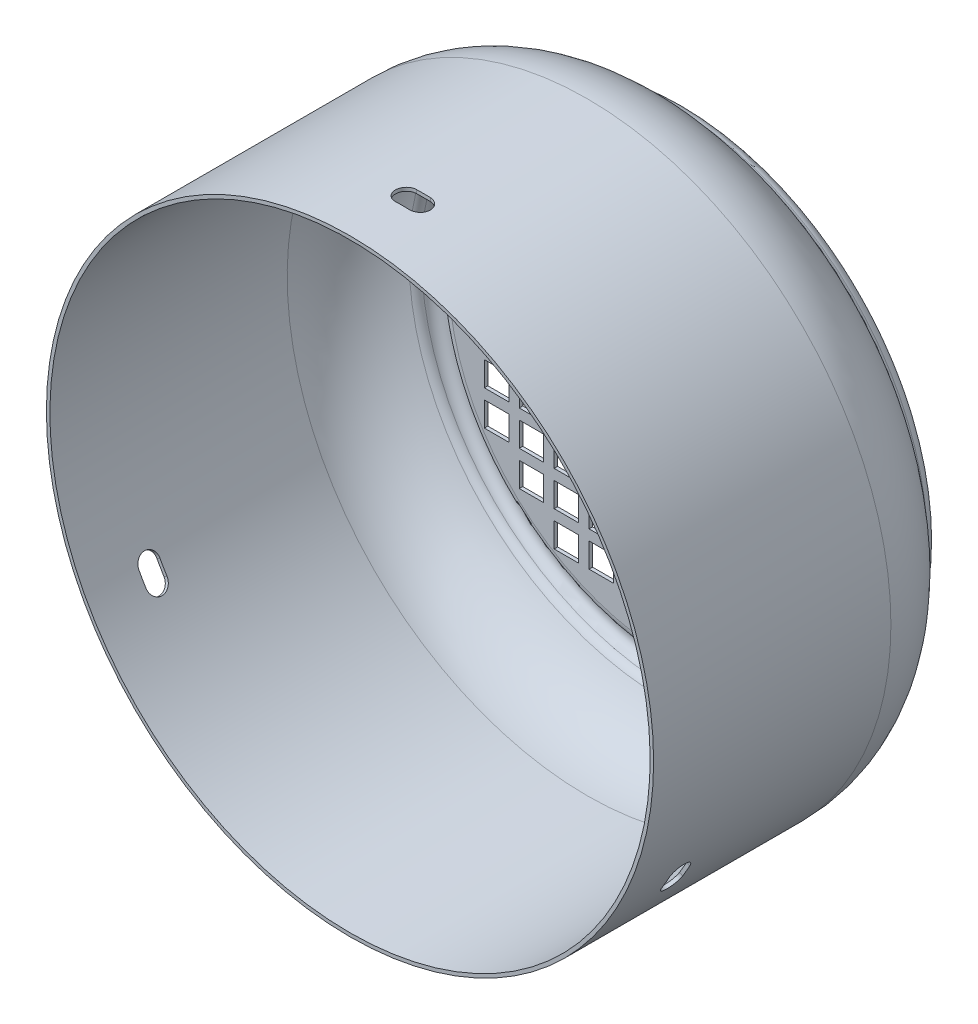
SolidWorks part; units mm, degrees
material "Q235"
ref_plane "前视基准面" through (0, 0, 0) normal (0, 0, 1) x (1, 0, 0)
ref_plane "上视基准面" through (0, 0, 0) normal (0, 1, 0) x (1, 0, 0)
ref_plane "右视基准面" through (0, 0, 0) normal (1, 0, 0) x (0, 0, -1)
sketch "草图1" plane through (0, 0, 0) normal (1, 0, 0) x (0, 0, -1)
  line L0 (0, 86) -> (0, 0)
  line L1 (0, 0) -> (92, 0) construction
  line L4 (92, 63.8038) -> (92, 0)
  line L5 (0, 86) -> (68, 86)
  arc A0 (93.5, 66.4019) -> (92.4282, 71.9693) centre (92, 69) ccw
  arc A1 (90.285, 73.3932) -> (68, 86) centre (68, 60) ccw
  arc A2 (90.285, 73.3932) -> (92.4282, 71.9693) centre (92.8564, 74.9386) ccw
  arc A3 (92, 63.8038) -> (93.5, 66.4019) centre (95, 63.8038) cw
  point P15 (92, 66)
  dimension "D1" = 3
revolve "旋转-薄壁2" add sketch "草图1" angle 360 about L1 wall 1
sketch "草图2" plane through (0, 0, -93) normal (0, 0, -1) x (-1, 0, 0)
  line L0 (-3.5, 3.5) -> (3.5, 3.5)
  line L1 (3.5, 3.5) -> (3.5, -3.5)
  line L2 (3.5, -3.5) -> (-3.5, -3.5)
  line L3 (-3.5, -3.5) -> (-3.5, 3.5)
  line L4 (13.5, -3.5) -> (6.5, -3.5)
  line L5 (13.5, 3.5) -> (13.5, -3.5)
  line L6 (6.5, -3.5) -> (6.5, 3.5)
  line L7 (6.5, 3.5) -> (13.5, 3.5)
  line L8 (23.5, -3.5) -> (16.5, -3.5)
  line L9 (23.5, 3.5) -> (23.5, -3.5)
  line L10 (16.5, -3.5) -> (16.5, 3.5)
  line L11 (16.5, 3.5) -> (23.5, 3.5)
  line L12 (33.5, -3.5) -> (26.5, -3.5)
  line L13 (33.5, 3.5) -> (33.5, -3.5)
  line L14 (26.5, -3.5) -> (26.5, 3.5)
  line L15 (26.5, 3.5) -> (33.5, 3.5)
  line L16 (43.5, -3.5) -> (36.5, -3.5)
  line L17 (43.5, 3.5) -> (43.5, -3.5)
  line L18 (36.5, -3.5) -> (36.5, 3.5)
  line L19 (36.5, 3.5) -> (43.5, 3.5)
  line L20 (53.5, -3.5) -> (46.5, -3.5)
  line L21 (53.5, 3.5) -> (53.5, -3.5)
  line L22 (46.5, -3.5) -> (46.5, 3.5)
  line L23 (46.5, 3.5) -> (53.5, 3.5)
  line L24 (3.5, 6.5) -> (-3.5, 6.5)
  line L25 (3.5, 13.5) -> (3.5, 6.5)
  line L26 (-3.5, 6.5) -> (-3.5, 13.5)
  line L27 (-3.5, 13.5) -> (3.5, 13.5)
  line L32 (23.5, 6.5) -> (16.5, 6.5)
  line L33 (23.5, 13.5) -> (23.5, 6.5)
  line L34 (16.5, 6.5) -> (16.5, 13.5)
  line L35 (16.5, 13.5) -> (23.5, 13.5)
  line L36 (33.5, 6.5) -> (26.5, 6.5)
  line L37 (33.5, 13.5) -> (33.5, 6.5)
  line L38 (26.5, 6.5) -> (26.5, 13.5)
  line L39 (26.5, 13.5) -> (33.5, 13.5)
  line L40 (43.5, 6.5) -> (36.5, 6.5)
  line L41 (43.5, 13.5) -> (43.5, 6.5)
  line L42 (36.5, 6.5) -> (36.5, 13.5)
  line L43 (36.5, 13.5) -> (43.5, 13.5)
  line L44 (53.5, 6.5) -> (46.5, 6.5)
  line L45 (53.5, 13.5) -> (53.5, 6.5)
  line L46 (46.5, 6.5) -> (46.5, 13.5)
  line L47 (46.5, 13.5) -> (53.5, 13.5)
  line L48 (3.5, 16.5) -> (-3.5, 16.5)
  line L49 (3.5, 23.5) -> (3.5, 16.5)
  line L50 (-3.5, 16.5) -> (-3.5, 23.5)
  line L51 (-3.5, 23.5) -> (3.5, 23.5)
  line L52 (13.5, 16.5) -> (6.5, 16.5)
  line L53 (13.5, 23.5) -> (13.5, 16.5)
  line L54 (6.5, 16.5) -> (6.5, 23.5)
  line L55 (6.5, 23.5) -> (13.5, 23.5)
  line L56 (23.5, 16.5) -> (16.5, 16.5)
  line L57 (23.5, 23.5) -> (23.5, 16.5)
  line L58 (16.5, 16.5) -> (16.5, 23.5)
  line L59 (16.5, 23.5) -> (23.5, 23.5)
  line L60 (33.5, 16.5) -> (26.5, 16.5)
  line L61 (33.5, 23.5) -> (33.5, 16.5)
  line L62 (26.5, 16.5) -> (26.5, 23.5)
  line L63 (26.5, 23.5) -> (33.5, 23.5)
  line L64 (43.5, 16.5) -> (36.5, 16.5)
  line L65 (43.5, 23.5) -> (43.5, 16.5)
  line L66 (36.5, 16.5) -> (36.5, 23.5)
  line L67 (36.5, 23.5) -> (43.5, 23.5)
  line L68 (53.5, 16.5) -> (46.5, 16.5)
  line L69 (53.5, 23.5) -> (53.5, 16.5)
  line L70 (46.5, 16.5) -> (46.5, 23.5)
  line L71 (46.5, 23.5) -> (53.5, 23.5)
  line L72 (3.5, 26.5) -> (-3.5, 26.5)
  line L73 (3.5, 33.5) -> (3.5, 26.5)
  line L74 (-3.5, 26.5) -> (-3.5, 33.5)
  line L75 (-3.5, 33.5) -> (3.5, 33.5)
  line L76 (13.5, 26.5) -> (6.5, 26.5)
  line L77 (13.5, 33.5) -> (13.5, 26.5)
  line L78 (6.5, 26.5) -> (6.5, 33.5)
  line L79 (6.5, 33.5) -> (13.5, 33.5)
  line L80 (23.5, 26.5) -> (16.5, 26.5)
  line L81 (23.5, 33.5) -> (23.5, 26.5)
  line L82 (16.5, 26.5) -> (16.5, 33.5)
  line L83 (16.5, 33.5) -> (23.5, 33.5)
  line L84 (33.5, 26.5) -> (26.5, 26.5)
  line L85 (33.5, 33.5) -> (33.5, 26.5)
  line L86 (26.5, 26.5) -> (26.5, 33.5)
  line L87 (26.5, 33.5) -> (33.5, 33.5)
  line L88 (43.5, 26.5) -> (36.5, 26.5)
  line L89 (43.5, 33.5) -> (43.5, 26.5)
  line L90 (36.5, 26.5) -> (36.5, 33.5)
  line L91 (36.5, 33.5) -> (43.5, 33.5)
  line L92 (53.5, 26.5) -> (46.5, 26.5)
  line L93 (53.5, 33.5) -> (53.5, 26.5)
  line L94 (46.5, 26.5) -> (46.5, 33.5)
  line L95 (46.5, 33.5) -> (53.5, 33.5)
  line L96 (3.5, 36.5) -> (-3.5, 36.5)
  line L97 (3.5, 43.5) -> (3.5, 36.5)
  line L98 (-3.5, 36.5) -> (-3.5, 43.5)
  line L99 (-3.5, 43.5) -> (3.5, 43.5)
  line L100 (13.5, 36.5) -> (6.5, 36.5)
  line L101 (13.5, 43.5) -> (13.5, 36.5)
  line L102 (6.5, 36.5) -> (6.5, 43.5)
  line L103 (6.5, 43.5) -> (13.5, 43.5)
  line L104 (23.5, 36.5) -> (16.5, 36.5)
  line L105 (23.5, 43.5) -> (23.5, 36.5)
  line L106 (16.5, 36.5) -> (16.5, 43.5)
  line L107 (16.5, 43.5) -> (23.5, 43.5)
  line L108 (33.5, 36.5) -> (26.5, 36.5)
  line L109 (33.5, 43.5) -> (33.5, 36.5)
  line L110 (26.5, 36.5) -> (26.5, 43.5)
  line L111 (26.5, 43.5) -> (33.5, 43.5)
  line L112 (43.5, 36.5) -> (36.5, 36.5)
  line L113 (43.5, 43.5) -> (43.5, 36.5)
  line L114 (36.5, 36.5) -> (36.5, 43.5)
  line L115 (36.5, 43.5) -> (43.5, 43.5)
  line L117 (-26.5, 53.5) -> (-33.5, 53.5)
  line L118 (-26.5, 46.5) -> (-26.5, 53.5)
  line L119 (-33.5, 53.5) -> (-33.5, 46.5)
  line L120 (3.5, 46.5) -> (-3.5, 46.5)
  line L121 (3.5, 53.5) -> (3.5, 46.5)
  line L122 (-3.5, 46.5) -> (-3.5, 53.5)
  line L123 (-3.5, 53.5) -> (3.5, 53.5)
  line L124 (13.5, 46.5) -> (6.5, 46.5)
  line L125 (13.5, 53.5) -> (13.5, 46.5)
  line L126 (6.5, 46.5) -> (6.5, 53.5)
  line L127 (6.5, 53.5) -> (13.5, 53.5)
  line L128 (23.5, 46.5) -> (16.5, 46.5)
  line L129 (23.5, 53.5) -> (23.5, 46.5)
  line L130 (16.5, 46.5) -> (16.5, 53.5)
  line L131 (16.5, 53.5) -> (23.5, 53.5)
  line L132 (33.5, 46.5) -> (26.5, 46.5)
  line L133 (33.5, 53.5) -> (33.5, 46.5)
  line L134 (26.5, 46.5) -> (26.5, 53.5)
  line L135 (26.5, 53.5) -> (33.5, 53.5)
  line L136 (-33.5, 46.5) -> (-26.5, 46.5)
  line L137 (-16.5, 53.5) -> (-23.5, 53.5)
  line L138 (-16.5, 46.5) -> (-16.5, 53.5)
  line L139 (-23.5, 53.5) -> (-23.5, 46.5)
  line L140 (-23.5, 46.5) -> (-16.5, 46.5)
  line L141 (-6.5, 53.5) -> (-13.5, 53.5)
  line L142 (-6.5, 46.5) -> (-6.5, 53.5)
  line L143 (-13.5, 53.5) -> (-13.5, 46.5)
  line L144 (43.5, 46.5) -> (36.5, 46.5) [skipped]
  line L145 (36.5, 46.5) -> (36.5, 53.5) [skipped]
  line L146 (36.5, 53.5) -> (43.5, 53.5) [skipped]
  line L147 (43.5, 53.5) -> (43.5, 46.5) [skipped]
  line L148 (46.5, 46.5) -> (46.5, 53.5) [skipped]
  line L149 (46.5, 53.5) -> (53.5, 53.5) [skipped]
  line L150 (53.5, 46.5) -> (46.5, 46.5) [skipped]
  line L151 (53.5, 53.5) -> (53.5, 46.5) [skipped]
  line L152 (46.5, 43.5) -> (53.5, 43.5) [skipped]
  line L153 (53.5, 43.5) -> (53.5, 36.5) [skipped]
  line L154 (53.5, 36.5) -> (46.5, 36.5) [skipped]
  line L155 (46.5, 36.5) -> (46.5, 43.5) [skipped]
  line L156 (-13.5, 46.5) -> (-6.5, 46.5)
  line L157 (-36.5, 43.5) -> (-43.5, 43.5)
  line L158 (-36.5, 36.5) -> (-36.5, 43.5)
  line L159 (-43.5, 43.5) -> (-43.5, 36.5)
  line L160 (-43.5, 36.5) -> (-36.5, 36.5)
  line L161 (-26.5, 43.5) -> (-33.5, 43.5)
  line L162 (-26.5, 36.5) -> (-26.5, 43.5)
  line L163 (-33.5, 43.5) -> (-33.5, 36.5)
  line L164 (-33.5, 36.5) -> (-26.5, 36.5)
  line L165 (-16.5, 43.5) -> (-23.5, 43.5)
  line L166 (-16.5, 36.5) -> (-16.5, 43.5)
  line L167 (-23.5, 43.5) -> (-23.5, 36.5)
  line L168 (-23.5, 36.5) -> (-16.5, 36.5)
  line L169 (-6.5, 43.5) -> (-13.5, 43.5)
  line L170 (-6.5, 36.5) -> (-6.5, 43.5)
  line L171 (-13.5, 43.5) -> (-13.5, 36.5)
  line L172 (-13.5, 36.5) -> (-6.5, 36.5)
  line L173 (-46.5, 33.5) -> (-53.5, 33.5)
  line L174 (-46.5, 26.5) -> (-46.5, 33.5)
  line L175 (-53.5, 33.5) -> (-53.5, 26.5)
  line L176 (-53.5, 26.5) -> (-46.5, 26.5)
  line L177 (-36.5, 33.5) -> (-43.5, 33.5)
  line L178 (-36.5, 26.5) -> (-36.5, 33.5)
  line L179 (-43.5, 33.5) -> (-43.5, 26.5)
  line L180 (-43.5, 26.5) -> (-36.5, 26.5)
  line L181 (-26.5, 33.5) -> (-33.5, 33.5)
  line L182 (-26.5, 26.5) -> (-26.5, 33.5)
  line L183 (-33.5, 33.5) -> (-33.5, 26.5)
  line L184 (-33.5, 26.5) -> (-26.5, 26.5)
  line L185 (-16.5, 33.5) -> (-23.5, 33.5)
  line L186 (-16.5, 26.5) -> (-16.5, 33.5)
  line L187 (-23.5, 33.5) -> (-23.5, 26.5)
  line L188 (-23.5, 26.5) -> (-16.5, 26.5)
  line L189 (-6.5, 33.5) -> (-13.5, 33.5)
  line L190 (-6.5, 26.5) -> (-6.5, 33.5)
  line L191 (-13.5, 33.5) -> (-13.5, 26.5)
  line L192 (-13.5, 26.5) -> (-6.5, 26.5)
  line L193 (-46.5, 23.5) -> (-53.5, 23.5)
  line L194 (-46.5, 16.5) -> (-46.5, 23.5)
  line L195 (-53.5, 23.5) -> (-53.5, 16.5)
  line L196 (-53.5, 16.5) -> (-46.5, 16.5)
  line L197 (-36.5, 23.5) -> (-43.5, 23.5)
  line L198 (-36.5, 16.5) -> (-36.5, 23.5)
  line L199 (-43.5, 23.5) -> (-43.5, 16.5)
  line L200 (-43.5, 16.5) -> (-36.5, 16.5)
  line L201 (-26.5, 23.5) -> (-33.5, 23.5)
  line L202 (-26.5, 16.5) -> (-26.5, 23.5)
  line L203 (-33.5, 23.5) -> (-33.5, 16.5)
  line L204 (-33.5, 16.5) -> (-26.5, 16.5)
  line L205 (-16.5, 23.5) -> (-23.5, 23.5)
  line L206 (-16.5, 16.5) -> (-16.5, 23.5)
  line L207 (-23.5, 23.5) -> (-23.5, 16.5)
  line L208 (-23.5, 16.5) -> (-16.5, 16.5)
  line L209 (-6.5, 23.5) -> (-13.5, 23.5)
  line L210 (-6.5, 16.5) -> (-6.5, 23.5)
  line L211 (-13.5, 23.5) -> (-13.5, 16.5)
  line L212 (-13.5, 16.5) -> (-6.5, 16.5)
  line L213 (-46.5, 13.5) -> (-53.5, 13.5)
  line L214 (-46.5, 6.5) -> (-46.5, 13.5)
  line L215 (-53.5, 13.5) -> (-53.5, 6.5)
  line L216 (-53.5, 6.5) -> (-46.5, 6.5)
  line L217 (-36.5, 13.5) -> (-43.5, 13.5)
  line L218 (-36.5, 6.5) -> (-36.5, 13.5)
  line L219 (-43.5, 13.5) -> (-43.5, 6.5)
  line L220 (-43.5, 6.5) -> (-36.5, 6.5)
  line L221 (-26.5, 13.5) -> (-33.5, 13.5)
  line L222 (-26.5, 6.5) -> (-26.5, 13.5)
  line L223 (-33.5, 13.5) -> (-33.5, 6.5)
  line L224 (-33.5, 6.5) -> (-26.5, 6.5)
  line L225 (-16.5, 13.5) -> (-23.5, 13.5)
  line L226 (-16.5, 6.5) -> (-16.5, 13.5)
  line L227 (-23.5, 13.5) -> (-23.5, 6.5)
  line L228 (-23.5, 6.5) -> (-16.5, 6.5)
  line L233 (-46.5, 3.5) -> (-53.5, 3.5)
  line L234 (-46.5, -3.5) -> (-46.5, 3.5)
  line L235 (-53.5, 3.5) -> (-53.5, -3.5)
  line L236 (-53.5, -3.5) -> (-46.5, -3.5)
  line L237 (-36.5, 3.5) -> (-43.5, 3.5)
  line L238 (-36.5, -3.5) -> (-36.5, 3.5)
  line L239 (-43.5, 3.5) -> (-43.5, -3.5)
  line L240 (-43.5, -3.5) -> (-36.5, -3.5)
  line L241 (-26.5, 3.5) -> (-33.5, 3.5)
  line L242 (-26.5, -3.5) -> (-26.5, 3.5)
  line L243 (-33.5, 3.5) -> (-33.5, -3.5)
  line L244 (-33.5, -3.5) -> (-26.5, -3.5)
  line L245 (-16.5, 3.5) -> (-23.5, 3.5)
  line L246 (-16.5, -3.5) -> (-16.5, 3.5)
  line L247 (-23.5, 3.5) -> (-23.5, -3.5)
  line L248 (-23.5, -3.5) -> (-16.5, -3.5)
  line L249 (-6.5, 3.5) -> (-13.5, 3.5)
  line L250 (-6.5, -3.5) -> (-6.5, 3.5)
  line L251 (-13.5, 3.5) -> (-13.5, -3.5)
  line L252 (-13.5, -3.5) -> (-6.5, -3.5)
  line L257 (-23.5, -6.5) -> (-16.5, -6.5)
  line L258 (-23.5, -13.5) -> (-23.5, -6.5)
  line L259 (-16.5, -6.5) -> (-16.5, -13.5)
  line L260 (-16.5, -13.5) -> (-23.5, -13.5)
  line L261 (-33.5, -6.5) -> (-26.5, -6.5)
  line L262 (-33.5, -13.5) -> (-33.5, -6.5)
  line L263 (-26.5, -6.5) -> (-26.5, -13.5)
  line L264 (-26.5, -13.5) -> (-33.5, -13.5)
  line L265 (-43.5, -6.5) -> (-36.5, -6.5)
  line L266 (-43.5, -13.5) -> (-43.5, -6.5)
  line L267 (-36.5, -6.5) -> (-36.5, -13.5)
  line L268 (-36.5, -13.5) -> (-43.5, -13.5)
  line L269 (-53.5, -6.5) -> (-46.5, -6.5)
  line L270 (-53.5, -13.5) -> (-53.5, -6.5)
  line L271 (-46.5, -6.5) -> (-46.5, -13.5)
  line L272 (-46.5, -13.5) -> (-53.5, -13.5)
  line L273 (-13.5, -16.5) -> (-6.5, -16.5)
  line L274 (-13.5, -23.5) -> (-13.5, -16.5)
  line L275 (-6.5, -16.5) -> (-6.5, -23.5)
  line L276 (-6.5, -23.5) -> (-13.5, -23.5)
  line L277 (-23.5, -16.5) -> (-16.5, -16.5)
  line L278 (-23.5, -23.5) -> (-23.5, -16.5)
  line L279 (-16.5, -16.5) -> (-16.5, -23.5)
  line L280 (-16.5, -23.5) -> (-23.5, -23.5)
  line L281 (-33.5, -16.5) -> (-26.5, -16.5)
  line L282 (-33.5, -23.5) -> (-33.5, -16.5)
  line L283 (-26.5, -16.5) -> (-26.5, -23.5)
  line L284 (-26.5, -23.5) -> (-33.5, -23.5)
  line L285 (-43.5, -16.5) -> (-36.5, -16.5)
  line L286 (-43.5, -23.5) -> (-43.5, -16.5)
  line L287 (-36.5, -16.5) -> (-36.5, -23.5)
  line L288 (-36.5, -23.5) -> (-43.5, -23.5)
  line L289 (-53.5, -16.5) -> (-46.5, -16.5)
  line L290 (-53.5, -23.5) -> (-53.5, -16.5)
  line L291 (-46.5, -16.5) -> (-46.5, -23.5)
  line L292 (-46.5, -23.5) -> (-53.5, -23.5)
  line L293 (-13.5, -26.5) -> (-6.5, -26.5)
  line L294 (-13.5, -33.5) -> (-13.5, -26.5)
  line L295 (-6.5, -26.5) -> (-6.5, -33.5)
  line L296 (-6.5, -33.5) -> (-13.5, -33.5)
  line L297 (-23.5, -26.5) -> (-16.5, -26.5)
  line L298 (-23.5, -33.5) -> (-23.5, -26.5)
  line L299 (-16.5, -26.5) -> (-16.5, -33.5)
  line L300 (-16.5, -33.5) -> (-23.5, -33.5)
  line L301 (-33.5, -26.5) -> (-26.5, -26.5)
  line L302 (-33.5, -33.5) -> (-33.5, -26.5)
  line L303 (-26.5, -26.5) -> (-26.5, -33.5)
  line L304 (-26.5, -33.5) -> (-33.5, -33.5)
  line L305 (-43.5, -26.5) -> (-36.5, -26.5)
  line L306 (-43.5, -33.5) -> (-43.5, -26.5)
  line L307 (-36.5, -26.5) -> (-36.5, -33.5)
  line L308 (-36.5, -33.5) -> (-43.5, -33.5)
  line L309 (-53.5, -26.5) -> (-46.5, -26.5)
  line L310 (-53.5, -33.5) -> (-53.5, -26.5)
  line L311 (-46.5, -26.5) -> (-46.5, -33.5)
  line L312 (-46.5, -33.5) -> (-53.5, -33.5)
  line L313 (-13.5, -36.5) -> (-6.5, -36.5)
  line L314 (-13.5, -43.5) -> (-13.5, -36.5)
  line L315 (-6.5, -36.5) -> (-6.5, -43.5)
  line L316 (-6.5, -43.5) -> (-13.5, -43.5)
  line L317 (-23.5, -36.5) -> (-16.5, -36.5)
  line L318 (-23.5, -43.5) -> (-23.5, -36.5)
  line L319 (-16.5, -36.5) -> (-16.5, -43.5)
  line L320 (-16.5, -43.5) -> (-23.5, -43.5)
  line L321 (-33.5, -36.5) -> (-26.5, -36.5)
  line L322 (-33.5, -43.5) -> (-33.5, -36.5)
  line L323 (-26.5, -36.5) -> (-26.5, -43.5)
  line L324 (-26.5, -43.5) -> (-33.5, -43.5)
  line L325 (-43.5, -36.5) -> (-36.5, -36.5)
  line L326 (-43.5, -43.5) -> (-43.5, -36.5)
  line L327 (-36.5, -36.5) -> (-36.5, -43.5)
  line L328 (-36.5, -43.5) -> (-43.5, -43.5)
  line L329 (-13.5, -46.5) -> (-6.5, -46.5)
  line L330 (-13.5, -53.5) -> (-13.5, -46.5)
  line L331 (-6.5, -46.5) -> (-6.5, -53.5)
  line L332 (-6.5, -53.5) -> (-13.5, -53.5)
  line L333 (-23.5, -46.5) -> (-16.5, -46.5)
  line L334 (-23.5, -53.5) -> (-23.5, -46.5)
  line L335 (-16.5, -46.5) -> (-16.5, -53.5)
  line L336 (-16.5, -53.5) -> (-23.5, -53.5)
  line L337 (-33.5, -46.5) -> (-26.5, -46.5)
  line L338 (26.5, -53.5) -> (33.5, -53.5)
  line L339 (26.5, -46.5) -> (26.5, -53.5)
  line L340 (33.5, -53.5) -> (33.5, -46.5)
  line L341 (33.5, -46.5) -> (26.5, -46.5)
  line L342 (16.5, -53.5) -> (23.5, -53.5)
  line L343 (16.5, -46.5) -> (16.5, -53.5)
  line L344 (23.5, -53.5) -> (23.5, -46.5)
  line L345 (23.5, -46.5) -> (16.5, -46.5)
  line L346 (6.5, -53.5) -> (13.5, -53.5)
  line L347 (6.5, -46.5) -> (6.5, -53.5)
  line L348 (13.5, -53.5) -> (13.5, -46.5)
  line L349 (13.5, -46.5) -> (6.5, -46.5)
  line L350 (-3.5, -53.5) -> (3.5, -53.5)
  line L351 (-3.5, -46.5) -> (-3.5, -53.5)
  line L352 (3.5, -53.5) -> (3.5, -46.5)
  line L353 (3.5, -46.5) -> (-3.5, -46.5)
  line L354 (-33.5, -53.5) -> (-33.5, -46.5)
  line L355 (-26.5, -46.5) -> (-26.5, -53.5)
  line L356 (-26.5, -53.5) -> (-33.5, -53.5)
  line L357 (36.5, -43.5) -> (43.5, -43.5)
  line L358 (36.5, -36.5) -> (36.5, -43.5)
  line L359 (43.5, -43.5) -> (43.5, -36.5)
  line L360 (43.5, -36.5) -> (36.5, -36.5)
  line L361 (26.5, -43.5) -> (33.5, -43.5)
  line L362 (26.5, -36.5) -> (26.5, -43.5)
  line L363 (33.5, -43.5) -> (33.5, -36.5)
  line L364 (33.5, -36.5) -> (26.5, -36.5)
  line L365 (16.5, -43.5) -> (23.5, -43.5)
  line L366 (16.5, -36.5) -> (16.5, -43.5)
  line L367 (23.5, -43.5) -> (23.5, -36.5)
  line L368 (23.5, -36.5) -> (16.5, -36.5)
  line L369 (6.5, -43.5) -> (13.5, -43.5)
  line L370 (6.5, -36.5) -> (6.5, -43.5)
  line L371 (13.5, -43.5) -> (13.5, -36.5)
  line L372 (13.5, -36.5) -> (6.5, -36.5)
  line L373 (-3.5, -43.5) -> (3.5, -43.5)
  line L374 (-3.5, -36.5) -> (-3.5, -43.5)
  line L375 (3.5, -43.5) -> (3.5, -36.5)
  line L376 (3.5, -36.5) -> (-3.5, -36.5)
  line L377 (46.5, -33.5) -> (53.5, -33.5)
  line L378 (46.5, -26.5) -> (46.5, -33.5)
  line L379 (53.5, -33.5) -> (53.5, -26.5)
  line L380 (53.5, -26.5) -> (46.5, -26.5)
  line L381 (36.5, -33.5) -> (43.5, -33.5)
  line L382 (36.5, -26.5) -> (36.5, -33.5)
  line L383 (43.5, -33.5) -> (43.5, -26.5)
  line L384 (43.5, -26.5) -> (36.5, -26.5)
  line L385 (26.5, -33.5) -> (33.5, -33.5)
  line L386 (26.5, -26.5) -> (26.5, -33.5)
  line L387 (33.5, -33.5) -> (33.5, -26.5)
  line L388 (33.5, -26.5) -> (26.5, -26.5)
  line L389 (16.5, -33.5) -> (23.5, -33.5)
  line L390 (16.5, -26.5) -> (16.5, -33.5)
  line L391 (23.5, -33.5) -> (23.5, -26.5)
  line L392 (23.5, -26.5) -> (16.5, -26.5)
  line L393 (6.5, -33.5) -> (13.5, -33.5)
  line L394 (6.5, -26.5) -> (6.5, -33.5)
  line L395 (13.5, -33.5) -> (13.5, -26.5)
  line L396 (13.5, -26.5) -> (6.5, -26.5)
  line L397 (-3.5, -33.5) -> (3.5, -33.5)
  line L398 (-3.5, -26.5) -> (-3.5, -33.5)
  line L399 (3.5, -33.5) -> (3.5, -26.5)
  line L400 (3.5, -26.5) -> (-3.5, -26.5)
  line L401 (46.5, -23.5) -> (53.5, -23.5)
  line L402 (46.5, -16.5) -> (46.5, -23.5)
  line L403 (53.5, -23.5) -> (53.5, -16.5)
  line L404 (53.5, -16.5) -> (46.5, -16.5)
  line L405 (36.5, -23.5) -> (43.5, -23.5)
  line L406 (36.5, -16.5) -> (36.5, -23.5)
  line L407 (43.5, -23.5) -> (43.5, -16.5)
  line L408 (43.5, -16.5) -> (36.5, -16.5)
  line L409 (26.5, -23.5) -> (33.5, -23.5)
  line L410 (26.5, -16.5) -> (26.5, -23.5)
  line L411 (33.5, -23.5) -> (33.5, -16.5)
  line L412 (33.5, -16.5) -> (26.5, -16.5)
  line L413 (16.5, -23.5) -> (23.5, -23.5)
  line L414 (16.5, -16.5) -> (16.5, -23.5)
  line L415 (23.5, -23.5) -> (23.5, -16.5)
  line L416 (23.5, -16.5) -> (16.5, -16.5)
  line L417 (6.5, -23.5) -> (13.5, -23.5)
  line L418 (6.5, -16.5) -> (6.5, -23.5)
  line L419 (13.5, -23.5) -> (13.5, -16.5)
  line L420 (13.5, -16.5) -> (6.5, -16.5)
  line L421 (-3.5, -23.5) -> (3.5, -23.5)
  line L422 (-3.5, -16.5) -> (-3.5, -23.5)
  line L423 (3.5, -23.5) -> (3.5, -16.5)
  line L424 (3.5, -16.5) -> (-3.5, -16.5)
  line L425 (46.5, -13.5) -> (53.5, -13.5)
  line L426 (46.5, -6.5) -> (46.5, -13.5)
  line L427 (53.5, -13.5) -> (53.5, -6.5)
  line L428 (53.5, -6.5) -> (46.5, -6.5)
  line L429 (36.5, -13.5) -> (43.5, -13.5)
  line L430 (36.5, -6.5) -> (36.5, -13.5)
  line L431 (43.5, -13.5) -> (43.5, -6.5)
  line L432 (43.5, -6.5) -> (36.5, -6.5)
  line L433 (26.5, -13.5) -> (33.5, -13.5)
  line L434 (26.5, -6.5) -> (26.5, -13.5)
  line L435 (33.5, -13.5) -> (33.5, -6.5)
  line L436 (33.5, -6.5) -> (26.5, -6.5)
  line L437 (16.5, -13.5) -> (23.5, -13.5)
  line L438 (16.5, -6.5) -> (16.5, -13.5)
  line L439 (23.5, -13.5) -> (23.5, -6.5)
  line L440 (23.5, -6.5) -> (16.5, -6.5)
  line L445 (-3.5, -13.5) -> (3.5, -13.5)
  line L446 (-3.5, -6.5) -> (-3.5, -13.5)
  line L447 (3.5, -13.5) -> (3.5, -6.5)
  line L448 (3.5, -6.5) -> (-3.5, -6.5)
  line L449 (13.5, 6.5) -> (6.5, 6.5) [skipped]
  line L450 (6.5, 6.5) -> (6.5, 13.5) [skipped]
  line L451 (6.5, 13.5) -> (13.5, 13.5) [skipped]
  line L452 (13.5, 13.5) -> (13.5, 6.5) [skipped]
extrude "拉伸1" cut sketch "草图2" against normal through all
sketch "草图3" plane through (0, 0, 0) normal (0, 1, 0) x (1, 0, 0)
  line L2 (-2, 21) -> (2, 21)
  line L3 (-2, 15) -> (2, 15)
  arc A0 (2, 15) -> (2, 21) centre (2, 18) ccw
  arc A1 (-2, 15) -> (-2, 21) centre (-2, 18) cw
extrude "拉伸2" cut sketch "草图3" along normal blind 90
pattern_circular "阵列(圆周)1" count 3 over 360 of "拉伸2"
scale "缩放比例1" scale about origin uniform scaling yes scale factor 0.25
